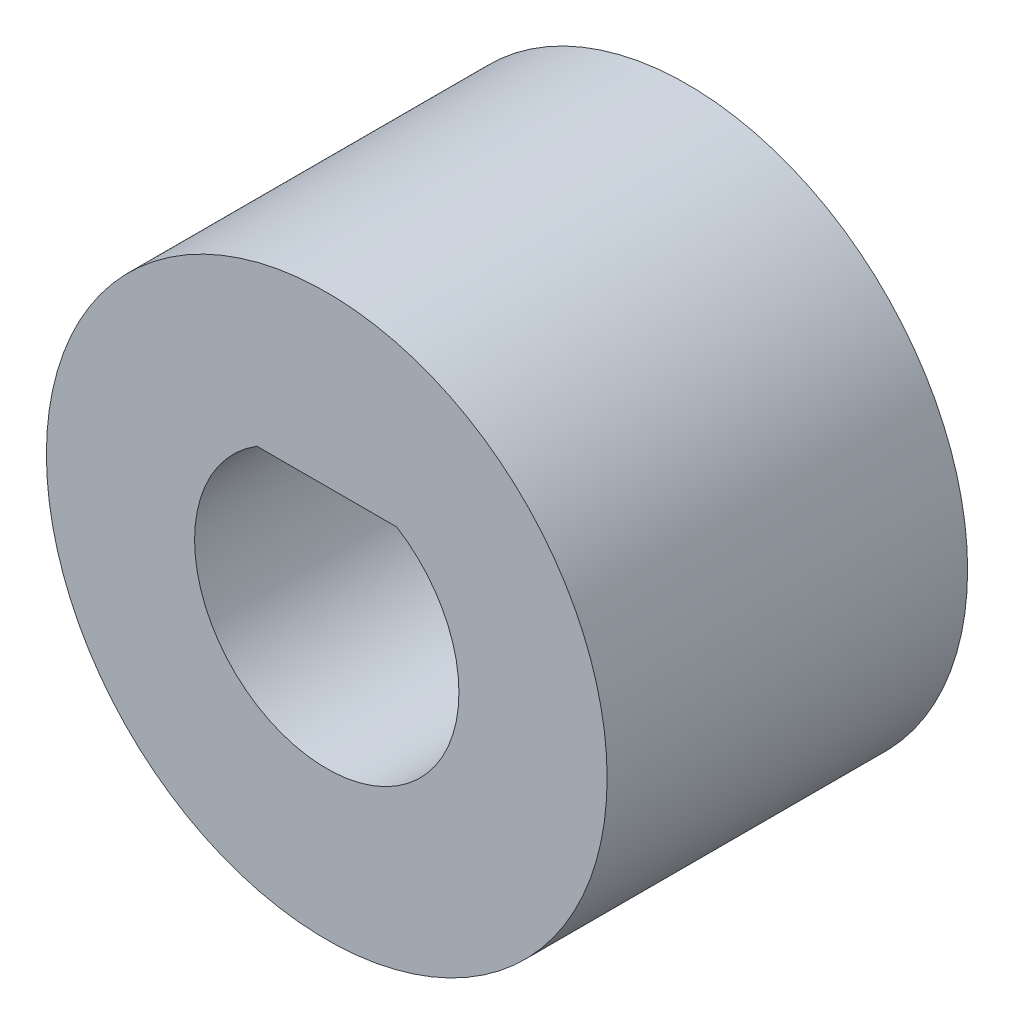
SolidWorks part; units mm, degrees
ref_plane "Plan de face" through (0, 0, 0) normal (0, 0, 1) x (1, 0, 0)
ref_plane "Plan de dessus" through (0, 0, 0) normal (0, 1, 0) x (1, 0, 0)
ref_plane "Plan de droite" through (0, 0, 0) normal (1, 0, 0) x (0, 0, -1)
sketch "Esquisse1" plane through (0, 0, 0) normal (0, 0, 1) x (1, 0, 0)
  line L0 (-1.7464, 2.8) -> (1.7464, 2.8)
  line L1 (-0.9885, -3.3) -> (1.037, -3.3) construction
  circle A0 centre (0, 0) radius 7
  arc A1 (-1.7464, 2.8) -> (1.7464, 2.8) centre (0, 0) ccw
  dimension "D1" = 14
  dimension "D2" = 6.6
  dimension "D3" = 6.1
extrude "Boss.-Extru.1" add sketch "Esquisse1" along normal blind 9
